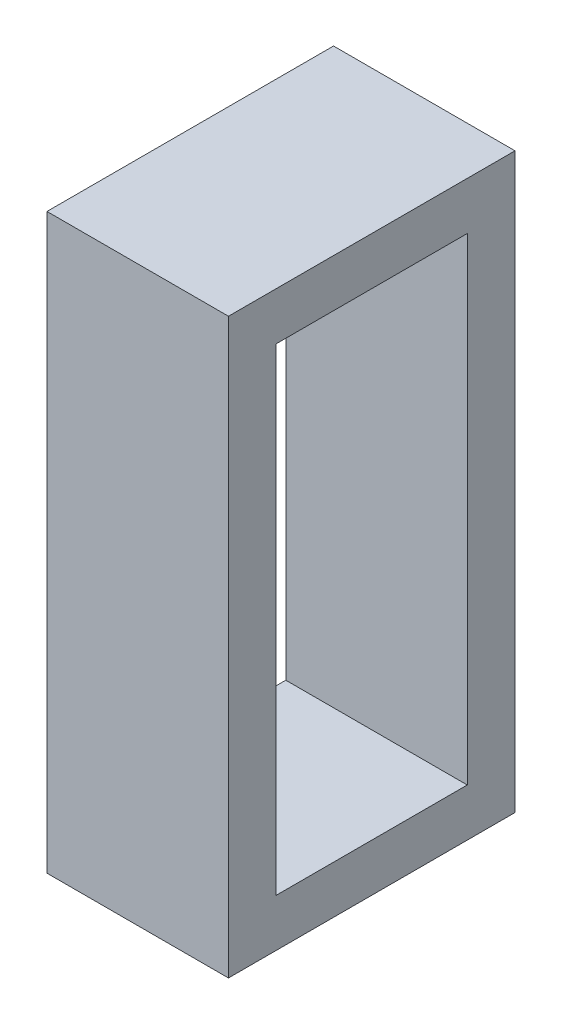
SolidWorks part; units mm, degrees
ref_plane "Front Plane" through (0, 0, 0) normal (0, 0, 1) x (1, 0, 0)
ref_plane "Top Plane" through (0, 0, 0) normal (0, 1, 0) x (1, 0, 0)
ref_plane "Right Plane" through (0, 0, 0) normal (1, 0, 0) x (0, 0, -1)
sketch "Sketch1" plane through (0, 0, 0) normal (0, 0, 1) x (1, 0, 0)
  line L4 (63.5, 38.1) -> (-63.5, 38.1)
  line L5 (63.5, -38.1) -> (63.5, 38.1)
  line L6 (-63.5, -38.1) -> (63.5, -38.1)
  line L7 (-63.5, 38.1) -> (-63.5, -38.1)
  line L8 (63.5, 38.1) -> (-63.5, 38.1)
  line L9 (63.5, -38.1) -> (63.5, 38.1)
  line L10 (-63.5, -38.1) -> (63.5, -38.1)
  line L11 (-63.5, 38.1) -> (-63.5, -38.1)
  circle A1 centre (25.4, 0) radius 12.7
  circle A2 centre (25.4, 0) radius 12.7
  dimension "D1" = 0
  dimension "D2" = 0
sketch "Sketch2" plane through (0, 0, 0) normal (0, 1, 0) x (1, 0, 0)
  line L4 (-63.5, 12.7) -> (-63.5, -25.4)
  line L5 (-63.5, -25.4) -> (63.5, -25.4)
  line L6 (63.5, -25.4) -> (63.5, 0)
  line L7 (-18.5941, 12.7) -> (-63.5, 12.7)
  line L8 (-63.5, 12.7) -> (-63.5, -25.4)
  line L9 (-63.5, -25.4) -> (63.5, -25.4)
  line L10 (63.5, -25.4) -> (63.5, 0)
  line L11 (-18.5941, 12.7) -> (-63.5, 12.7)
  arc A3 (63.5, 0) -> (25.4, 38.1) centre (25.4, 0) ccw
  arc A4 (25.4, 38.1) -> (-7.5956, 19.05) centre (25.4, 0) ccw
  arc A5 (-18.5941, 12.7) -> (-7.5956, 19.05) centre (-18.5941, 25.4) ccw
  arc A6 (63.5, 0) -> (25.4, 38.1) centre (25.4, 0) ccw
  arc A7 (25.4, 38.1) -> (-7.5956, 19.05) centre (25.4, 0) ccw
  arc A8 (-18.5941, 12.7) -> (-7.5956, 19.05) centre (-18.5941, 25.4) ccw
  dimension "D1" = 0
sketch "Sketch3" plane through (0, 0, 0) normal (0, 1, 0) x (1, 0, 0)
  line L0 (25.4, 50.8) -> (25.4, -38.1) construction
  line L1 (25.4, 50.8) -> (25.4, -38.1)
sketch "Sketch4" plane through (-88.9, 0, 0) normal (-1, 0, 0) x (0, 0, 1)
  line L8 (19.05, 31.75) -> (-6.35, 31.75)
  line L9 (-6.35, 31.75) -> (-6.35, -31.75)
  line L10 (-6.35, -31.75) -> (19.05, -31.75)
  line L11 (19.05, -31.75) -> (19.05, 31.75)
  line L12 (19.05, 31.75) -> (-6.35, 31.75)
  line L13 (-6.35, 31.75) -> (-6.35, -31.75)
  line L14 (-6.35, -31.75) -> (19.05, -31.75)
  line L15 (19.05, -31.75) -> (19.05, 31.75)
  line L16 (-12.7, 38.1) -> (-12.7, -38.1)
  line L17 (-12.7, -38.1) -> (25.4, -38.1)
  line L18 (25.4, -38.1) -> (25.4, 38.1)
  line L19 (25.4, 38.1) -> (-12.7, 38.1)
  line L20 (-12.7, 38.1) -> (-12.7, -38.1)
  line L21 (-12.7, -38.1) -> (25.4, -38.1)
  line L22 (25.4, -38.1) -> (25.4, 38.1)
  line L23 (25.4, 38.1) -> (-12.7, 38.1)
  dimension "D1" = 1.27
  dimension "D2" = 0
extrude "Boss-Extrude1" add sketch "Sketch4" against normal offset from surface (24.13 mm away) 1.27
